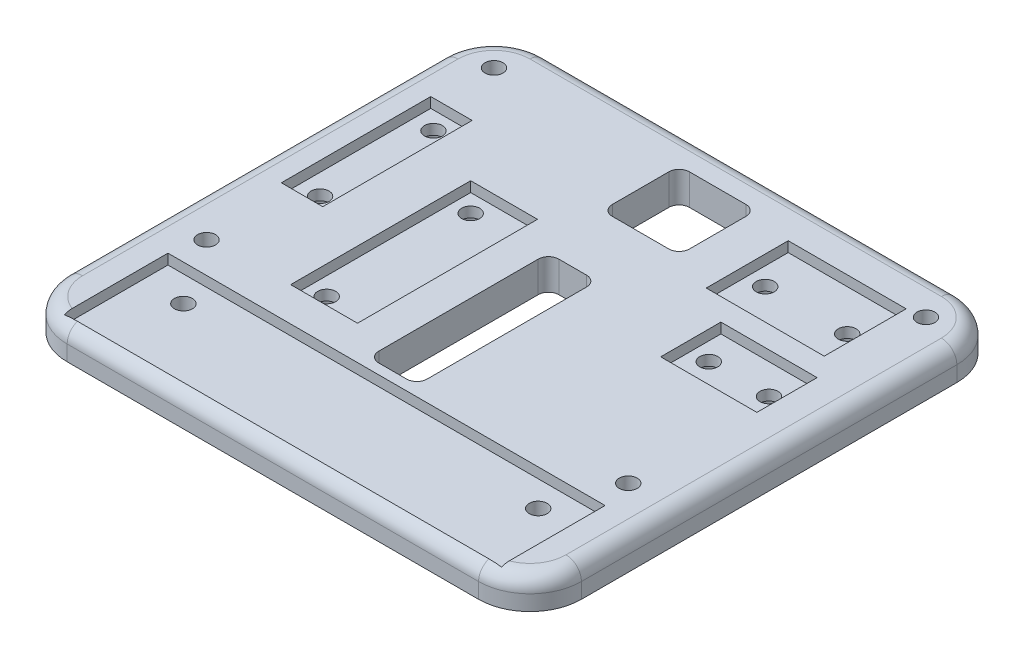
SolidWorks part; units mm, degrees
ref_plane "Plano frontal" through (0, 0, 0) normal (0, 0, 1) x (1, 0, 0)
ref_plane "Plano superior" through (0, 0, 0) normal (0, 1, 0) x (1, 0, 0)
ref_plane "Plano direito" through (0, 0, 0) normal (1, 0, 0) x (0, 0, -1)
sketch "Esboço1" plane through (0, 0, 0) normal (0, 1, 0) x (1, 0, 0)
  line L1 (-50, -46.5) -> (50, -46.5)
  line L2 (-50, -46.5) -> (-50, 46.5)
  line L3 (-50, 46.5) -> (50, 46.5)
  line L4 (50, -46.5) -> (50, 46.5)
  line L5 (-50, -46.5) -> (50, 46.5) construction
  line L6 (-50, 46.5) -> (50, -46.5) construction
  point P0 (0, 0)
  dimension "D1" = 100
  dimension "D2" = 93
extrude "Ressalto-extrusão1" add sketch "Esboço1" along normal blind 6
fillet "Filete1" radius 10 4 edges at (50, 3, -46.5) (50, 3, 46.5) (-50, 3, 46.5) (-50, 3, -46.5)
fillet "Filete2" radius 3 8 edges at (0, 6, -46.5) (47.0711, 6, -43.5711) (50, 6, 0) (47.0711, 6, 43.5711) (0, 6, 46.5) (-47.0711, 6, 43.5711) (-50, 6, 0) (-47.0711, 6, -43.5711)
sketch "Esboço2" plane through (0, 6, 0) normal (0, 1, 0) x (1, 0, 0)
  line L0 (-50, -46.5) -> (50, -46.5) construction
  line L1 (-42.5, -44.5) -> (42.5, -44.5)
  line L2 (-42.5, -44.5) -> (-42.5, -24.4)
  line L3 (-42.5, -24.4) -> (42.5, -24.4)
  line L4 (42.5, -44.5) -> (42.5, -24.4)
  point P5 (0, -24.4)
  dimension "D1" = 85
  dimension "D2" = 20.1
  dimension "D3" = 2
extrude "Corte-extrusão1" cut sketch "Esboço2" against normal blind 2
sketch "Esboço8" plane through (0, 4, 0) normal (0, 1, 0) x (1, 0, 0)
  line L0 (0, 13.4049) -> (0, -62.6773) construction
  line L1 (42.5, -43.0383) -> (42.5, -24.4) construction
  line L3 (42.5, -24.4) -> (-42.5, -24.4) construction
  circle A0 centre (34.5, -29.4) radius 1.75
  circle A1 centre (-34.5, -29.4) radius 1.75
  dimension "D1" = 3.5
  dimension "D2" = 8
  dimension "D3" = 5
extrude "Corte-extrusão6" cut sketch "Esboço8" against normal up to next
ref_plane "Plano1" through (0, 0, 42) normal (0, 0, -1) x (-1, 0, 0)
ref_axis "Eixo1" through (0, -0.3095, 42) along (0, 1, 0)
sketch "Esboço5" plane through (0, 6, 0) normal (0, 1, 0) x (1, 0, 0)
  line L1 (-43.325, -1.525) -> (-35.275, -1.525)
  line L2 (-43.325, -1.525) -> (-43.325, 27.525)
  line L3 (-43.325, 27.525) -> (-35.275, 27.525)
  line L4 (-35.275, -1.525) -> (-35.275, 27.525)
  line L5 (-43.325, -1.525) -> (-35.275, 27.525) construction
  line L6 (-43.325, 27.525) -> (-35.275, -1.525) construction
  point P0 (-39.3, 13)
  dimension "D1" = 55
  dimension "D2" = 39.3
  dimension "D3" = 8.05
  dimension "D4" = 29.05
extrude "Corte-extrusão3" cut sketch "Esboço5" against normal up to surface (2 mm away) up to face at (-34.5, 4, 31.15)
sketch "Esboço13" plane through (0, 4, 0) normal (0, 1, 0) x (1, 0, 0)
  line L0 (-43.325, 13) -> (-35.275, 13) construction
  line L1 (-43.325, 27.525) -> (-43.325, -1.525) construction
  line L2 (-35.275, -1.525) -> (-35.275, 27.525) construction
  line L4 (-35.275, 27.525) -> (-43.325, 27.525) construction
  circle A0 centre (-39.3, 24.025) radius 1.75
  circle A1 centre (-39.3, 1.975) radius 1.75
  point P11 (-39.3, 13)
  dimension "D1" = 3.5
  dimension "D2" = 3.5
extrude "Corte-extrusão10" cut sketch "Esboço13" against normal up to next
sketch "Esboço14" plane through (0, 0, 0) normal (0, -1, 0) x (1, 0, 0)
  circle A0 centre (-39.3, -1.975) radius 3.25
  circle A1 centre (-39.3, -24.025) radius 3.25
  dimension "D1" = 6.5
extrude "Corte-extrusão11" cut sketch "Esboço14" against normal blind 2
sketch "Esboço6" plane through (0, 6, 0) normal (0, 1, 0) x (1, 0, 0)
  line L1 (15.71, 22.06) -> (38.65, 22.06)
  line L2 (15.71, 22.06) -> (15.71, 38)
  line L3 (15.71, 38) -> (38.65, 38)
  line L4 (38.65, 22.06) -> (38.65, 38)
  line L5 (15.71, 22.06) -> (38.65, 38) construction
  line L6 (15.71, 38) -> (38.65, 22.06) construction
  point P0 (27.18, 30.03)
  dimension "D1" = 72.03
  dimension "D2" = 27.18
  dimension "D3" = 22.94
  dimension "D4" = 15.94
extrude "Corte-extrusão4" cut sketch "Esboço6" against normal up to surface (2 mm away) up to face at (-34.5, 4, 31.15)
sketch "Esboço15" plane through (0, 4, 0) normal (0, 1, 0) x (1, 0, 0)
  line L0 (27.18, 38) -> (27.18, 22.06) construction
  line L4 (38.65, 38) -> (15.71, 38) construction
  line L5 (15.71, 22.06) -> (38.65, 22.06) construction
  line L6 (15.71, 38) -> (15.71, 22.06) construction
  circle A0 centre (19.21, 30.03) radius 1.75
  circle A1 centre (35.15, 30.03) radius 1.75
  point P12 (27.18, 30.03)
  dimension "D1" = 3.5
  dimension "D2" = 3.5
extrude "Corte-extrusão12" cut sketch "Esboço15" against normal up to next
sketch "Esboço16" plane through (0, 0, 0) normal (0, -1, 0) x (1, 0, 0)
  circle A0 centre (19.21, -30.03) radius 3.25
  circle A1 centre (35.15, -30.03) radius 3.25
  circle A2 centre (-39.3, -24.025) radius 3.25 construction
extrude "Corte-extrusão13" cut sketch "Esboço16" against normal blind 2
sketch "Esboço7" plane through (0, 6, 0) normal (0, 1, 0) x (1, 0, 0)
  line L1 (22.865, 6.045) -> (41.575, 6.045)
  line L2 (22.865, 6.045) -> (22.865, 17.755)
  line L3 (22.865, 17.755) -> (41.575, 17.755)
  line L4 (41.575, 6.045) -> (41.575, 17.755)
  line L5 (22.865, 6.045) -> (41.575, 17.755) construction
  line L6 (22.865, 17.755) -> (41.575, 6.045) construction
  point P0 (32.22, 11.9)
  dimension "D1" = 53.9
  dimension "D2" = 32.22
  dimension "D3" = 18.71
  dimension "D4" = 11.71
extrude "Corte-extrusão5" cut sketch "Esboço7" against normal up to surface (2 mm away) up to face at (-34.5, 4, 31.15)
sketch "Esboço11" plane through (0, 4, 0) normal (0, 1, 0) x (1, 0, 0)
  line L0 (32.22, 6.045) -> (32.22, 17.755) construction
  line L1 (22.865, 6.045) -> (41.575, 6.045) construction
  line L2 (41.575, 17.755) -> (22.865, 17.755) construction
  line L3 (22.865, 17.755) -> (22.865, 6.045) construction
  circle A0 centre (26.365, 11.9) radius 1.75
  circle A1 centre (38.075, 11.9) radius 1.75
  point P14 (32.22, 11.9)
  dimension "D1" = 3.5
  dimension "D2" = 3.5
extrude "Corte-extrusão8" cut sketch "Esboço11" against normal up to next
sketch "Esboço12" plane through (0, 0, 0) normal (0, -1, 0) x (1, 0, 0)
  circle A0 centre (26.365, -11.9) radius 3.25
  circle A1 centre (38.075, -11.9) radius 3.25
  dimension "D1" = 6.5
extrude "Corte-extrusão9" cut sketch "Esboço12" against normal blind 2
sketch "Esboço17" plane through (0, 6, 0) normal (0, 1, 0) x (1, 0, 0)
  line L1 (-25.27, 17.23) -> (-12.27, 17.23)
  line L2 (-25.27, 17.23) -> (-25.27, -17.77)
  line L3 (-25.27, -17.77) -> (-12.27, -17.77)
  line L4 (-12.27, 17.23) -> (-12.27, -17.77)
  line L5 (-25.27, 17.23) -> (-12.27, -17.77) construction
  line L6 (-25.27, -17.77) -> (-12.27, 17.23) construction
  point P0 (-18.77, -0.27)
  dimension "D1" = 13
  dimension "D2" = 35
  dimension "D3" = 41.73
  dimension "D4" = 12.27
extrude "Corte-extrusão14" cut sketch "Esboço17" against normal up to surface (2 mm away) up to face at (-34.5, 4, 31.15)
sketch "Esboço18" plane through (0, 4, 0) normal (0, 1, 0) x (1, 0, 0)
  line L0 (-25.27, -0.27) -> (-12.27, -0.27) construction
  line L1 (-25.27, 17.23) -> (-25.27, -17.77) construction
  line L2 (-12.27, -17.77) -> (-12.27, 17.23) construction
  line L3 (-12.27, 17.23) -> (-25.27, 17.23) construction
  line L4 (-25.27, 17.23) -> (-25.27, -17.77) construction
  circle A0 centre (-21.77, 13.73) radius 1.75
  circle A1 centre (-21.77, -14.27) radius 1.75
  dimension "D2" = 3.5
  dimension "D1" = 3.5
  dimension "D3" = 3.5
extrude "Corte-extrusão15" cut sketch "Esboço18" against normal up to next and the other way through all
sketch "Esboço19" plane through (0, 0, 0) normal (0, -1, 0) x (1, 0, 0)
  circle A0 centre (-21.77, 14.27) radius 3.25
  circle A1 centre (-21.77, -13.73) radius 3.25
  circle A3 centre (-39.3, -1.975) radius 3.25 construction
extrude "Corte-extrusão18" cut sketch "Esboço19" against normal up to surface (2 mm away) up to face at (-39.3, 2, -5.225)
sketch "Esboço20" plane through (0, 6, 0) normal (0, 1, 0) x (1, 0, 0)
  line L0 (42.5, -24.4) -> (-42.5, -24.4) construction
  line L1 (-5.5, 12.6) -> (3.9, 12.6)
  line L2 (-5.5, 12.6) -> (-5.5, -22.4)
  line L3 (-5.5, -22.4) -> (3.9, -22.4)
  line L4 (3.9, 12.6) -> (3.9, -22.4)
  line L5 (-12.27, -17.77) -> (-12.27, 17.23) construction
  dimension "D1" = 9.4
  dimension "D2" = 35
  dimension "D3" = 2
  dimension "D4" = 6.77
extrude "Corte-extrusão17" cut sketch "Esboço20" against normal up to next
sketch "Esboço21" plane through (0, 6, 0) normal (0, 1, 0) x (1, 0, 0)
  line L1 (-7.5, 40) -> (7.5, 40)
  line L2 (-7.5, 40) -> (-7.5, 25)
  line L3 (-7.5, 25) -> (7.5, 25)
  line L4 (7.5, 40) -> (7.5, 25)
  point P2 (0, 25)
  dimension "D1" = 15
  dimension "D2" = 25
extrude "Corte-extrusão19" cut sketch "Esboço21" against normal up to next
fillet "Filete3" radius 2 8 edges at (3.9, 3, -12.6) (-5.5, 3, -12.6) (-5.5, 3, 22.4) (3.9, 3, 22.4) (7.5, 3, -25) (-7.5, 3, -25) (7.5, 3, -40) (-7.5, 3, -40)
sketch "Esboço22" plane through (0, 6, 0) normal (0, 1, 0) x (1, 0, 0)
  line L0 (47, -36.5) -> (47, 36.5) construction
  line L1 (42.5, -24.4) -> (-42.5, -24.4) construction
  circle A0 centre (41, -18.4) radius 1.75
  dimension "D1" = 3.5
  dimension "D2" = 6
  dimension "D3" = 6
extrude "Corte-extrusão20" cut sketch "Esboço22" against normal up to next
sketch "Esboço23" plane through (0, 6, 0) normal (0, 1, 0) x (1, 0, 0)
  line L0 (40, 43.5) -> (-40, 43.5) construction
  line L1 (47, -36.5) -> (47, 36.5) construction
  circle A0 centre (42, 38.5) radius 1.75
  dimension "D1" = 3.5
  dimension "D2" = 5
  dimension "D3" = 5
extrude "Corte-extrusão21" cut sketch "Esboço23" against normal up to next
mirror "Espelhar1" about plane through (0, 0, 0) normal (1, 0, 0) of "Corte-extrusão21", "Corte-extrusão20"
